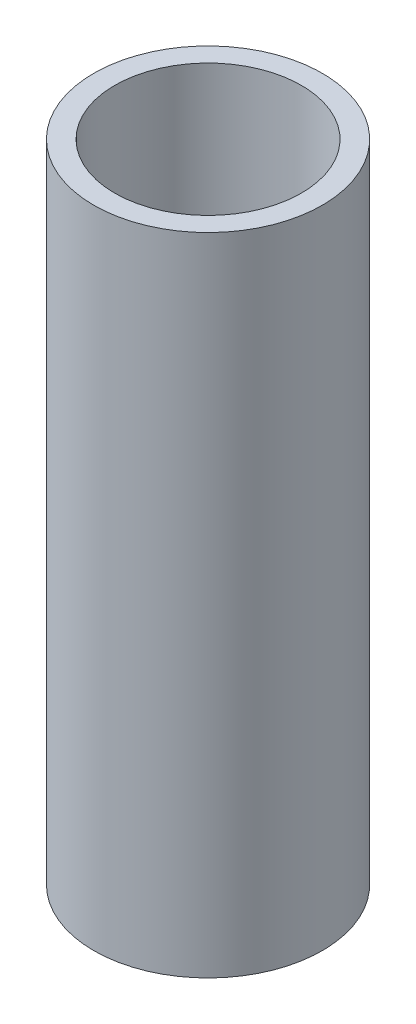
SolidWorks part; units mm, degrees
ref_plane "Front Plane" through (0, 0, 0) normal (0, 0, 1) x (1, 0, 0)
ref_plane "Top Plane" through (0, 0, 0) normal (0, 1, 0) x (1, 0, 0)
ref_plane "Right Plane" through (0, 0, 0) normal (1, 0, 0) x (0, 0, -1)
sketch "Sketch1" plane through (0, 0, 0) normal (0, 1, 0) x (1, 0, 0)
  circle A0 centre (0, 0) radius 60
  dimension "SLEEVE_OD" = 120
extrude "Boss-Extrude1" add sketch "Sketch1" along normal blind 338.923
sketch "Sketch2" plane through (0, 0, 0) normal (0, 1, 0) x (1, 0, 0)
  circle A0 centre (0, 0) radius 49.0148
  dimension "BORE_D" = 98.0295
extrude "Cut-Extrude1" cut sketch "Sketch2" along normal through all
chamfer "Chamfer1" distance 3.7412 angle 67.635 rebuild error yes
